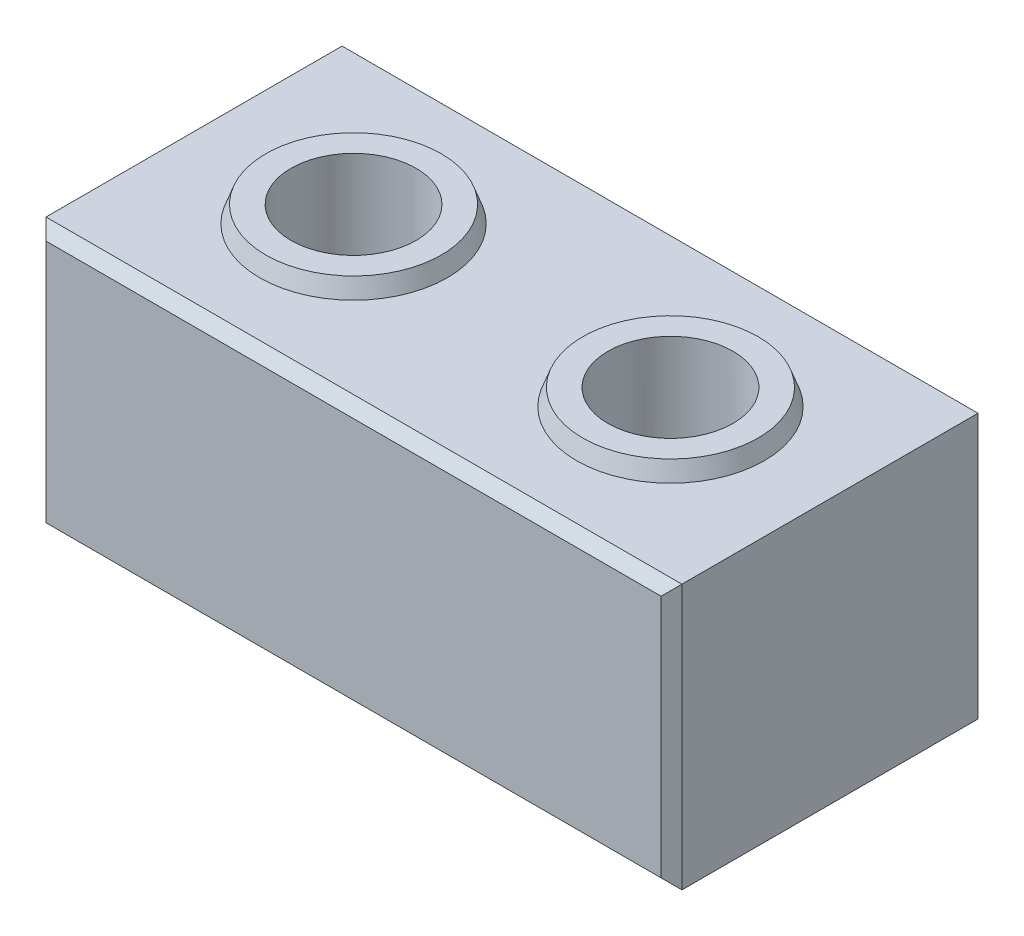
SolidWorks part; units mm, degrees
ref_plane "Front Plane" through (0, 0, 0) normal (0, 0, 1) x (1, 0, 0)
ref_plane "Top Plane" through (0, 0, 0) normal (0, 1, 0) x (1, 0, 0)
ref_plane "Right Plane" through (0, 0, 0) normal (1, 0, 0) x (0, 0, -1)
sketch "Sketch1" plane through (0, 0, 0) normal (0, 1, 0) x (1, 0, 0)
  line L1 (152.5, -76) -> (-152.5, -76)
  line L2 (152.5, -76) -> (152.5, 76)
  line L3 (152.5, 76) -> (-152.5, 76)
  line L4 (-152.5, -76) -> (-152.5, 76)
  line L5 (152.5, -76) -> (-152.5, 76) construction
  line L6 (152.5, 76) -> (-152.5, -76) construction
  point P0 (0, 0)
  dimension "D1" = 305
  dimension "D2" = 152
extrude "Boss-Extrude1" add sketch "Sketch1" against normal blind 127
sketch "Sketch2" plane through (0, 0, 0) normal (0, 1, 0) x (1, 0, 0)
  line L0 (0, 0) -> (0, 50000) construction
  line L1 (0, 0) -> (-50000, 0) construction
  line L2 (-76, 76) -> (-76, -76) construction
  line L3 (152.5, 76) -> (-152.5, 76) construction
  line L4 (-152.5, -76) -> (152.5, -76) construction
  circle A0 centre (-76, 0) radius 30
  circle A1 centre (76, 0) radius 30
  point P15 (0, 0)
  dimension "D2" = 60
  dimension "D1" = 76
extrude "Cut-Extrude1" cut sketch "Sketch2" against normal through all
sketch "Sketch3" plane through (0, 0, 0) normal (0, 1, 0) x (1, 0, 0)
  line L0 (0, 0) -> (0, 50000) construction
  line L1 (0, 0) -> (-50000, 0) construction
  circle A0 centre (-76, 0) radius 45
  circle A1 centre (76, 0) radius 45
  circle A2 centre (-76, 0) radius 30
  circle A3 centre (76, 0) radius 30
  dimension "D1" = 90
  dimension "D2" = 60
extrude "Boss-Extrude2" add sketch "Sketch3" along normal blind 8
chamfer "Chamfer1" distance 8 angle 20 2 edges at (76, 8, -45) (-76, 8, 45) first distance on face at (76, 8, -45) first distance on face at (-76, 8, 45)
sketch "Sketch4" plane through (0, -127, 0) normal (0, -1, 0) x (1, 0, 0)
  line L0 (0, 0) -> (0, 50000) construction
  line L1 (0, 0) -> (-50000, 0) construction
  circle A0 centre (-76, 0) radius 46
  circle A1 centre (-76, 0) radius 30
  circle A2 centre (76, 0) radius 46
  circle A3 centre (76, 0) radius 30
  dimension "D1" = 92
  dimension "D2" = 60
extrude "Cut-Extrude2" cut sketch "Sketch4" against normal blind 10
chamfer "Chamfer2" distance 10 angle 20 2 edges at (76, -117, 46) (-76, -117, -46) first distance on face at (76, -117, 46) first distance on face at (-76, -117, -46)
chamfer "Chamfer3" distance 5 distance2 5 8 edges at (0, 0, 76) (152.5, -63.5, 76) (-152.5, -63.5, 76) (0, -127, 76) (0, 0, -76) (-152.5, -63.5, -76) (152.5, -63.5, -76) (0, -127, -76)
